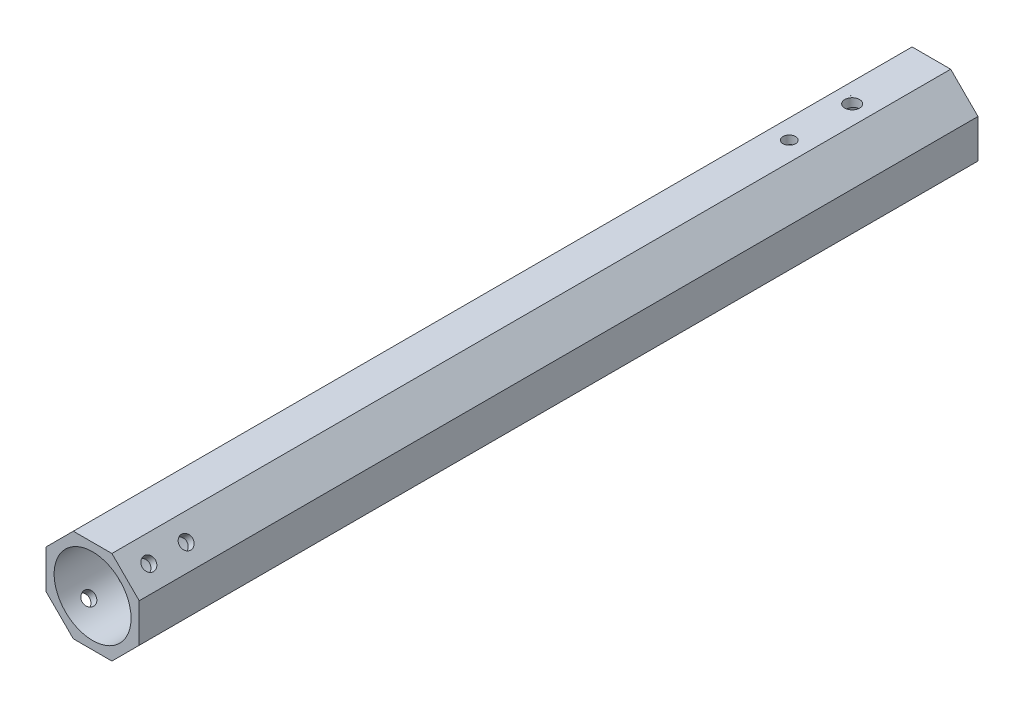
SolidWorks part; units mm, degrees
ref_plane "Front Plane" through (0, 0, 0) normal (0, 0, 1) x (1, 0, 0)
ref_plane "Top Plane" through (0, 0, 0) normal (0, 1, 0) x (1, 0, 0)
ref_plane "Right Plane" through (0, 0, 0) normal (1, 0, 0) x (0, 0, -1)
sketch "Sketch1" plane through (0, 0, 0) normal (0, 0, 1) x (1, 0, 0)
  line L6 (10, 4.1421) -> (4.1421, 10)
  line L7 (4.1421, 10) -> (-4.1421, 10)
  line L8 (-4.1421, 10) -> (-10, 4.1421)
  line L9 (-10, 4.1421) -> (-10, -4.1421)
  line L10 (-10, -4.1421) -> (-4.1421, -10)
  line L11 (-4.1421, -10) -> (4.1421, -10)
  line L12 (4.1421, -10) -> (10, -4.1421)
  line L13 (10, -4.1421) -> (10, 4.1421)
  circle A0 centre (0, 0) radius 8.25
  circle A1 centre (0, 0) radius 10 construction
  dimension "D1" = 16.5
  dimension "D2" = 20
extrude "Boss-Extrude1" add sketch "Sketch1" against normal up to surface (178 mm away)
sketch "Sketch2" plane through (0, 0, -178) normal (0, 0, -1) x (-1, 0, 0)
  line L8 (-10, 4.1421) -> (-10, -4.1421)
  line L9 (-10, -4.1421) -> (-4.1421, -10)
  line L10 (-4.1421, -10) -> (4.1421, -10)
  line L11 (4.1421, -10) -> (10, -4.1421)
  line L12 (10, -4.1421) -> (10, 4.1421)
  line L13 (10, 4.1421) -> (4.1421, 10)
  line L14 (4.1421, 10) -> (-4.1421, 10)
  line L15 (-4.1421, 10) -> (-10, 4.1421)
  line L16 (-10, 4.1421) -> (-10, -4.1421)
  line L17 (-10, -4.1421) -> (-4.1421, -10)
  line L18 (-4.1421, -10) -> (4.1421, -10)
  line L19 (4.1421, -10) -> (10, -4.1421)
  line L20 (10, -4.1421) -> (10, 4.1421)
  line L21 (10, 4.1421) -> (4.1421, 10)
  line L22 (4.1421, 10) -> (-4.1421, 10)
  line L23 (-4.1421, 10) -> (-10, 4.1421)
  dimension "D1" = 0
extrude "Boss-Extrude2" add sketch "Sketch2" along normal blind 2
sketch "Sketch4" plane through (0, 0, 0) normal (0, 1, 0) x (1, 0, 0)
  circle A9 centre (0, 149.5) radius 1.35 construction
  circle A10 centre (0, 163) radius 1.6 construction
  circle A11 centre (0, 149.5) radius 1.35
  circle A12 centre (0, 163) radius 1.6
extrude "Cut-Extrude1" cut sketch "Sketch4" against normal through all and the other way through all
sketch "Sketch6" plane through (-7.0711, 7.0711, 0) normal (-0.7071, 0.7071, 0) x (0, 0, 1)
  circle A0 centre (-13, 0) radius 1.4 construction
  circle A1 centre (-5, 0) radius 1.4 construction
  circle A2 centre (-13, 0) radius 1.4
  circle A3 centre (-5, 0) radius 1.4
extrude "Cut-Extrude2" cut sketch "Sketch6" against normal through all
ref_axis "Axis1" through (0, 0, 6.85) along (0, 0, -1)
pattern_circular "CirPattern1" count 2 every 270 about axis through (0, 0, 6.85) along (0, 0, -1) of "Cut-Extrude2"
sketch "Sketch7" plane through (0, 0, -180) normal (0, 0, -1) x (-1, 0, 0)
  circle A0 centre (0, 0) radius 6.2698
extrude "Cut-Extrude3" cut sketch "Sketch7" against normal through all
